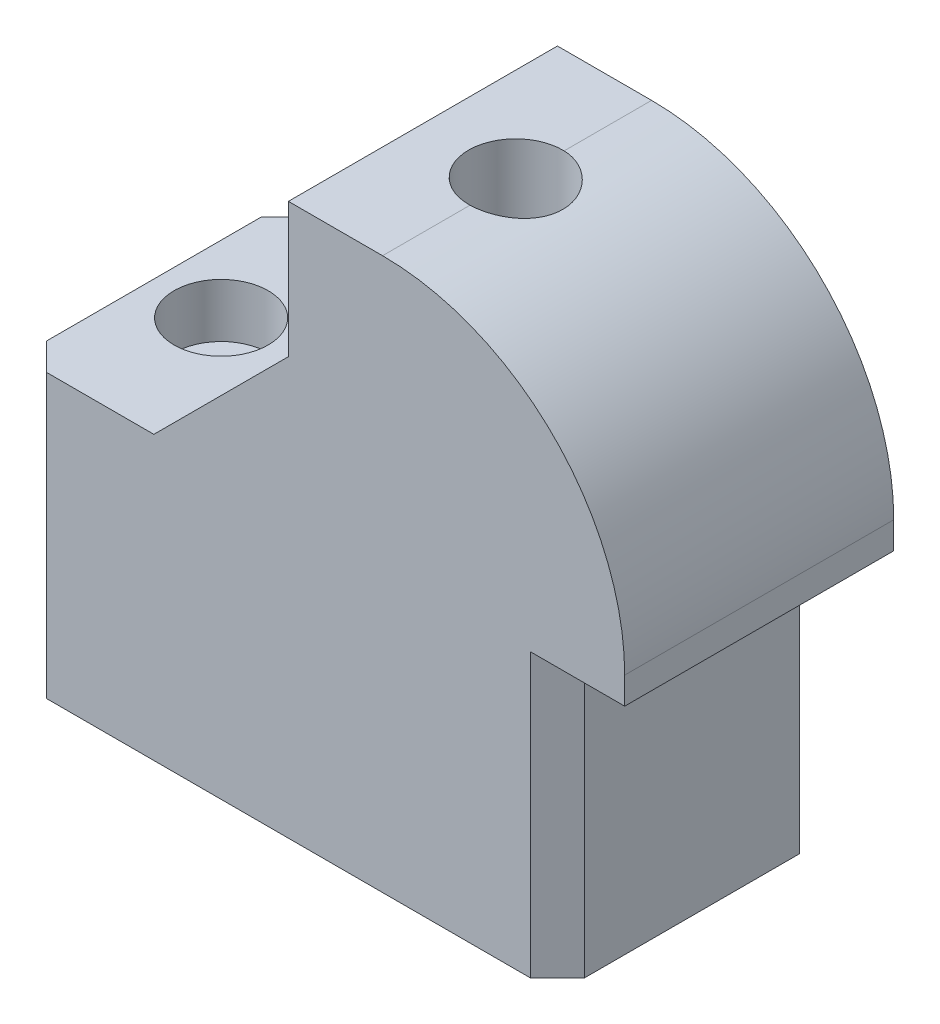
SolidWorks part; units mm, degrees
ref_plane "Front Plane" through (0, 0, 0) normal (0, 0, 1) x (1, 0, 0)
ref_plane "Top Plane" through (0, 0, 0) normal (0, 1, 0) x (1, 0, 0)
ref_plane "Right Plane" through (0, 0, 0) normal (1, 0, 0) x (0, 0, -1)
sketch "Sketch1" plane through (0, 0, 0) normal (0, 1, 0) x (1, 0, 0)
  line L1 (-12.7, 12.7) -> (12.7, 12.7)
  line L2 (-12.7, 12.7) -> (-12.7, -12.7)
  line L3 (-12.7, -12.7) -> (12.7, -12.7)
  line L4 (12.7, 12.7) -> (12.7, -12.7)
  line L5 (-12.7, 12.7) -> (12.7, -12.7) construction
  line L6 (-12.7, -12.7) -> (12.7, 12.7) construction
  line L7 (-12.7, -12.7) -> (-63.5, -12.7)
  line L8 (-12.7, -12.7) -> (-12.7, 12.7)
  line L9 (-12.7, 12.7) -> (-63.5, 12.7)
  line L10 (-63.5, -12.7) -> (-63.5, 12.7)
  point P0 (0, 0)
  dimension "D1" = 25.4
  dimension "D2" = 25.4
  dimension "D3" = 50.8
extrude "Boss-Extrude1" add sketch "Sketch1" along normal blind 26.67 contours L10 L7 L2 L9 region at (-38.1, 0, 0)
sketch "Sketch2" plane through (0, 26.67, 0) normal (0, 1, 0) x (1, 0, 0)
  line L1 (-12.7, 12.7) -> (-6.35, 12.7)
  line L2 (-12.7, 12.7) -> (-12.7, -12.7)
  line L3 (-12.7, -12.7) -> (-6.35, -12.7)
  line L4 (-6.35, 12.7) -> (-6.35, -12.7)
  dimension "D1" = 25.4
  dimension "D2" = 6.35
extrude "Boss-Extrude2" add sketch "Sketch2" along normal blind 25.4 separate body contours L2 L1 L4 L3
sketch "Sketch3" plane through (0, 26.67, 0) normal (0, 1, 0) x (1, 0, 0)
  line L0 (-12.7, -12.7) -> (-63.5, -12.7) construction
  line L1 (-12.7, 12.7) -> (-38.1, 12.7)
  line L2 (-12.7, 12.7) -> (-12.7, -12.7)
  line L3 (-12.7, -12.7) -> (-38.1, -12.7)
  line L4 (-38.1, 12.7) -> (-38.1, -12.7)
  dimension "D1" = 25.4
extrude "Boss-Extrude3" add sketch "Sketch3" along normal blind 25.4
chamfer "Chamfer1" distance 12.7 angle 45 1 edges at (-38.1, 26.67, 0)
chamfer "Chamfer2" [suppressed] distance 20.32 angle 35
sketch "Sketch4" plane through (0, 26.67, 0) normal (0, 1, 0) x (1, 0, 0)
  line L0 (-63.5, -12.7) -> (-63.5, 12.7) construction
  line L1 (-38.1, 12.7) -> (-38.1, -12.7) construction
  circle A0 centre (-57.15, 0) radius 2.413
  circle A1 centre (-29.3391, 0) radius 2.413
  circle A2 centre (-57.15, 0) radius 4.445
  circle A3 centre (-29.3391, 0) radius 4.445
  dimension "D1" = 4.826
  dimension "D2" = 4.826
  dimension "D3" = 8.89
  dimension "D4" = 8.89
  dimension "D5" = 6.35
  dimension "D6" = 8.7609
extrude "Cut-Extrude1" cut sketch "Sketch4" against normal through all contours A0 | A1
extrude "Cut-Extrude2" cut sketch "Sketch4<4>" against normal blind 5.08
sketch "Sketch4<4>" plane through (0, 26.67, 0) normal (0, 1, 0) x (1, 0, 0) same geometry as "Sketch4"
sketch "Sketch5" plane through (0, 52.07, 0) normal (0, 1, 0) x (1, 0, 0)
  line L0 (-38.1, 12.7) -> (-38.1, -12.7) construction
  circle A0 centre (-29.3391, 0) radius 4.445
  dimension "D1" = 8.89
  dimension "D2" = 8.7609
extrude "Cut-Extrude3" cut sketch "Sketch5" against normal blind 1.27 and the other way blind 29.972 from surface contours A0 starting at face at (-57.15, 26.67, 4.445)
chamfer "Chamfer3" distance 2.54 angle 45 4 edges at (-12.7, 13.335, -12.7) (-12.7, 13.335, 12.7) (-63.5, 13.335, 12.7) (-63.5, 13.335, -12.7)
fillet "Fillet1" radius 22.86 1 edges at (-6.35, 52.07, 0)
